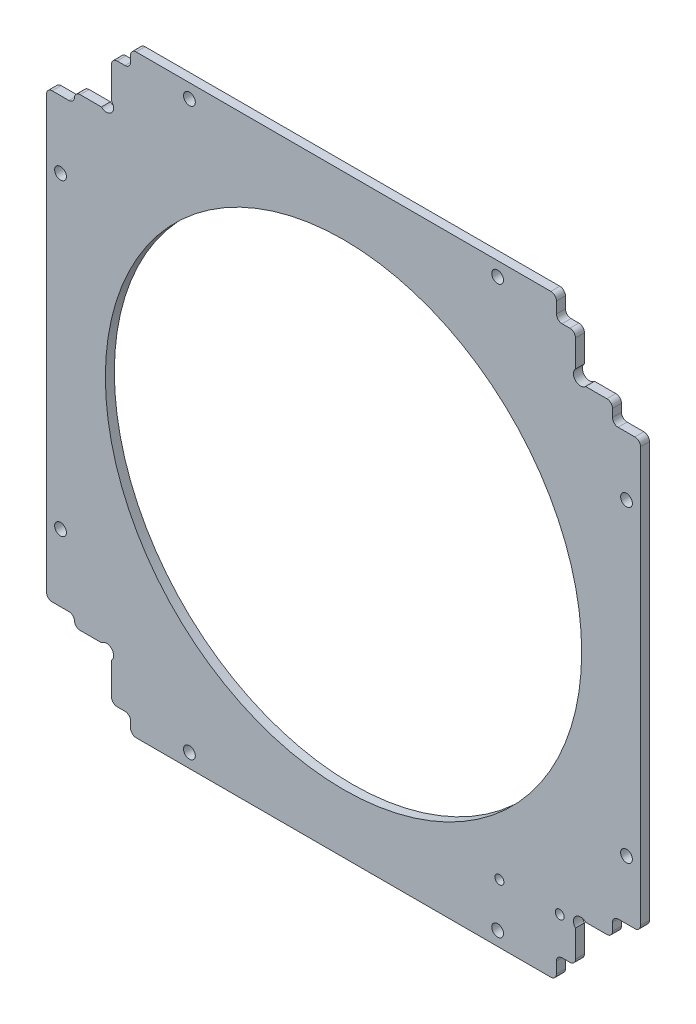
SolidWorks part; units mm, degrees
material "FR4_stuffedProtoboard"
ref_plane "Front Plane" through (0, 0, 0) normal (0, 0, 1) x (1, 0, 0)
ref_plane "Top Plane" through (0, 0, 0) normal (0, 1, 0) x (1, 0, 0)
ref_plane "Right Plane" through (0, 0, 0) normal (1, 0, 0) x (0, 0, -1)
sketch "Sketch1" plane through (0, 0, 0) normal (0, 0, 1) x (1, 0, 0)
  line L0 (53, 53) -> (-53, -53) construction
  line L1 (53, 53) -> (-53, 53)
  line L2 (53, 53) -> (53, -53)
  line L3 (53, -53) -> (-53, -53)
  line L4 (-53, 53) -> (-53, -53)
  point P4 (0, 0)
  dimension "D1" = 106
  dimension "D2" = 106
extrude "mainOutline" add sketch "Sketch1" along normal blind 1.6
sketch "axisLabels" plane through (0, 0, 0) normal (0, 0, -1) x (-1, 0, 0)
  text T0 "+Y"
  text T1 "+X"
sketch "Sketch4" plane through (0, 0, 0) normal (0, 0, -1) x (-1, 0, 0)
  line L1 (-41.4, -41.4) -> (-48, -41.4)
  line L3 (-41.4, -49) -> (-41.4, -41.4)
  line L5 (-60.1065, -39) -> (-49.9975, -39)
  line L7 (-39, -61.4521) -> (-39, -49.9)
  line L9 (39, -56.2753) -> (39, -49.9)
  line L10 (-53, 53) -> (53, 53) construction
  line L11 (41.4, -49.9) -> (41.4, -41.4)
  line L12 (-53, -53) -> (-53, 53) construction
  line L13 (41.4, -41.4) -> (48, -41.4)
  line L15 (48, -40.5) -> (55.5177, -40.5)
  line L17 (55.3838, 40.5) -> (48, 40.5)
  line L19 (39, 57.6877) -> (39, 49.9)
  line L21 (-39, 59.8804) -> (-39, 49.9)
  line L23 (-56.8428, 39) -> (-49.9975, 39)
  line L25 (-41.4, 41.4) -> (-41.4, 49)
  line L27 (-48, 41.4) -> (-41.4, 41.4)
  line L29 (41.4, 49.9) -> (41.4, 41.4)
  line L31 (48, 41.4) -> (41.4, 41.4)
  line L32 (-48, 41.4) -> (-48, 39)
  line L33 (-48, 39) -> (-49.9975, 39)
  line L34 (-41.4, 49) -> (-39, 49)
  line L35 (-39, 49) -> (-39, 49.9)
  line L36 (48, 40.5) -> (48, 41.4)
  line L37 (39, 49.9) -> (41.4, 49.9)
  line L38 (48, -40.5) -> (48, -41.4)
  line L39 (39, -49.9) -> (41.4, -49.9)
  line L40 (-41.4, -49) -> (-39, -49)
  line L41 (-39, -49) -> (-39, -49.9)
  line L42 (-49.9975, -39) -> (-48, -39)
  line L43 (-48, -39) -> (-48, -41.4)
  line L44 (-39, 59.8804) -> (-56.8428, 59.8804)
  line L45 (-56.8428, 59.8804) -> (-56.8428, 39)
  line L46 (53, 53) -> (53, -53) construction
  line L47 (-60.1065, -39) -> (-60.1065, -61.4521)
  line L48 (-60.1065, -61.4521) -> (-39, -61.4521)
  line L49 (39, -56.2753) -> (55.5177, -56.2753)
  line L50 (55.5177, -56.2753) -> (55.5177, -40.5)
  line L51 (55.3838, 40.5) -> (55.3838, 57.6877)
  line L52 (55.3838, 57.6877) -> (39, 57.6877)
  line L53 (53, -53) -> (-53, -53) construction
  dimension "D1" = 14
  dimension "D2" = 11.6
  dimension "D3" = 5
  dimension "D4" = 12.5
  dimension "D5" = 11.6
  dimension "D6" = 3.1
  dimension "D7" = 12.5
  dimension "D8" = 14
  dimension "D9" = 3.1
  dimension "D10" = 5
  dimension "D11" = 11.6
  dimension "D12" = 11.6
  dimension "D13" = 14
  dimension "D14" = 14
  dimension "D15" = 11.6
  dimension "D16" = 11.6
  dimension "D17" = 5
  dimension "D18" = 4
  dimension "D19" = 14
  dimension "D20" = 14
  dimension "D21" = 11.6
  dimension "D22" = 11.6
  dimension "D23" = 4
  dimension "D24" = 5
extrude "railCutouts" cut sketch "Sketch4" against normal through all
sketch "Sketch5" plane through (0, 0, 0) normal (0, 0, -1) x (-1, 0, 0)
  line L0 (-48.898, -39.898) -> (-52.4015, -43.4015) construction
  line L1 (-48, -40.7961) -> (-51.5035, -44.2995) construction
  line L2 (-49.7961, -39) -> (-53.2995, -42.5035) construction
  line L3 (-48, -41.4) -> (-48, -39) construction
  line L4 (-48, 39) -> (-48, 41.4) construction
  line L5 (-42.298, -42.298) -> (-45.4445, -45.4445) construction
  line L6 (-41.4, -43.1961) -> (-44.5465, -46.3425)
  line L7 (-43.1961, -41.4) -> (-46.3425, -44.5465)
  line L8 (-39.898, -49.898) -> (-42.6199, -52.6199) construction
  line L9 (-39, -50.7961) -> (-41.7219, -53.5179) construction
  line L10 (-40.7961, -49) -> (-43.5179, -51.7219) construction
  line L11 (39.898, -50.798) -> (41.4231, -52.3231) construction
  line L12 (40.7961, -49.9) -> (42.3212, -51.4251) construction
  line L13 (39, -51.6961) -> (40.5251, -53.2212) construction
  line L14 (42.298, -42.298) -> (44.0402, -44.0402) construction
  line L15 (43.1961, -41.4) -> (44.9382, -43.1422)
  line L16 (41.4, -43.1961) -> (43.1422, -44.9382)
  line L17 (48.898, -41.398) -> (49.9793, -42.4793) construction
  line L18 (49.7961, -40.5) -> (50.8774, -41.5813) construction
  line L19 (48, -42.2961) -> (49.0813, -43.3774) construction
  line L20 (48.898, 41.398) -> (50.5001, 43.0001) construction
  line L21 (48, 42.2961) -> (49.602, 43.8981) construction
  line L22 (49.7961, 40.5) -> (51.3981, 42.102) construction
  line L23 (42.298, 42.298) -> (44.029, 44.029) construction
  line L24 (41.4, 43.1961) -> (43.131, 44.927)
  line L25 (43.1961, 41.4) -> (44.927, 43.131)
  line L26 (39.898, 50.798) -> (41.2638, 52.1638) construction
  line L27 (39, 51.6961) -> (40.3658, 53.0618) construction
  line L28 (40.7961, 49.9) -> (42.1618, 51.2658) construction
  line L29 (-48.898, 39.898) -> (-50.0606, 41.0606) construction
  line L30 (-49.7961, 39) -> (-50.9587, 40.1626) construction
  line L31 (-48, 40.7961) -> (-49.1626, 41.9587) construction
  line L32 (-42.298, 42.298) -> (-43.7968, 43.7968) construction
  line L33 (-43.1961, 41.4) -> (-44.6948, 42.8988)
  line L34 (-41.4, 43.1961) -> (-42.8988, 44.6948)
  line L35 (-39.898, 49.898) -> (-41.256, 51.256) construction
  line L36 (-40.7961, 49) -> (-42.154, 50.358) construction
  line L37 (-39, 50.7961) -> (-40.358, 52.154) construction
  line L38 (-41.4, 41.4) -> (-41.4, 49) construction
  line L39 (-39, 49) -> (-39, 53) construction
  line L40 (39, 53) -> (39, 49.9) construction
  line L41 (41.4, 49.9) -> (41.4, 41.4) construction
  line L42 (48, 41.4) -> (48, 40.5) construction
  line L43 (39, -49.9) -> (39, -53) construction
  line L44 (41.4, -41.4) -> (41.4, -49.9) construction
  line L45 (53, -40.5) -> (48, -40.5) construction
  line L46 (-39, -53) -> (-39, -49) construction
  line L47 (-41.4, -49) -> (-41.4, -41.4) construction
  arc A0 (-48, -40.7961) -> (-49.7961, -39) centre (-48.898, -39.898) ccw construction
  arc A1 (-53.2995, -42.5035) -> (-51.5035, -44.2995) centre (-52.4015, -43.4015) ccw construction
  arc A2 (-41.4, -43.1961) -> (-43.1961, -41.4) centre (-42.298, -42.298) ccw
  arc A3 (-46.3425, -44.5465) -> (-44.5465, -46.3425) centre (-45.4445, -45.4445) ccw
  arc A4 (-39, -50.7961) -> (-40.7961, -49) centre (-39.898, -49.898) ccw construction
  arc A5 (-43.5179, -51.7219) -> (-41.7219, -53.5179) centre (-42.6199, -52.6199) ccw construction
  arc A6 (40.7961, -49.9) -> (39, -51.6961) centre (39.898, -50.798) ccw construction
  arc A7 (40.5251, -53.2212) -> (42.3212, -51.4251) centre (41.4231, -52.3231) ccw construction
  arc A8 (43.1961, -41.4) -> (41.4, -43.1961) centre (42.298, -42.298) ccw
  arc A9 (43.1422, -44.9382) -> (44.9382, -43.1422) centre (44.0402, -44.0402) ccw
  arc A10 (49.7961, -40.5) -> (48, -42.2961) centre (48.898, -41.398) ccw construction
  arc A11 (49.0813, -43.3774) -> (50.8774, -41.5813) centre (49.9793, -42.4793) ccw construction
  arc A12 (48, 42.2961) -> (49.7961, 40.5) centre (48.898, 41.398) ccw construction
  arc A13 (51.3981, 42.102) -> (49.602, 43.8981) centre (50.5001, 43.0001) ccw construction
  arc A14 (41.4, 43.1961) -> (43.1961, 41.4) centre (42.298, 42.298) ccw
  arc A15 (44.927, 43.131) -> (43.131, 44.927) centre (44.029, 44.029) ccw
  arc A16 (39, 51.6961) -> (40.7961, 49.9) centre (39.898, 50.798) ccw construction
  arc A17 (42.1618, 51.2658) -> (40.3658, 53.0618) centre (41.2638, 52.1638) ccw construction
  arc A18 (-49.7961, 39) -> (-48, 40.7961) centre (-48.898, 39.898) ccw construction
  arc A19 (-49.1626, 41.9587) -> (-50.9587, 40.1626) centre (-50.0606, 41.0606) ccw construction
  arc A20 (-43.1961, 41.4) -> (-41.4, 43.1961) centre (-42.298, 42.298) ccw
  arc A21 (-42.8988, 44.6948) -> (-44.6948, 42.8988) centre (-43.7968, 43.7968) ccw
  arc A22 (-40.7961, 49) -> (-39, 50.7961) centre (-39.898, 49.898) ccw construction
  arc A23 (-40.358, 52.154) -> (-42.154, 50.358) centre (-41.256, 51.256) ccw construction
  point P2 (-50.6498, -41.6498)
  point P9 (-43.8713, -43.8713)
  point P17 (-41.259, -51.259)
  point P24 (40.6606, -51.5606)
  point P31 (43.1691, -43.1691)
  point P38 (49.4387, -41.9387)
  point P45 (49.699, 42.199)
  point P52 (43.1635, 43.1635)
  point P59 (40.5809, 51.4809)
  point P66 (-49.4793, 40.4793)
  point P73 (-43.0474, 43.0474)
  point P80 (-40.577, 50.577)
  dimension "D14" = 1.27
  dimension "D1" = 45
  dimension "D3" = 45
  dimension "D4" = 45
  dimension "D5" = 45
  dimension "D6" = 45
  dimension "D7" = 45
  dimension "D8" = 45
  dimension "D9" = 45
  dimension "D10" = 45
  dimension "D11" = 45
  dimension "D12" = 45
  dimension "D13" = 45
extrude "dogbones" cut sketch "Sketch5" against normal through all
sketch "Sketch6" plane through (0, 0, 0) normal (0, 0, -1) x (-1, 0, 0)
  line L0 (-39, 50) -> (-39, 53) construction
  line L1 (-39, 49) -> (-39, 53) construction
  line L2 (-39, 53) -> (39, 53) construction
  line L3 (-40, 50) -> (-40, 53)
  line L4 (-38, 50) -> (-38, 53)
  line L5 (-49, 39) -> (-53, 39) construction
  line L6 (-53, 39) -> (-48, 39) construction
  line L7 (-49, 38) -> (-53, 38)
  line L8 (-49, 40) -> (-53, 40)
  line L9 (-49, -39) -> (-55.2142, -39) construction
  line L10 (-48, -39) -> (-53, -39) construction
  line L11 (-49, -40) -> (-55.2142, -40)
  line L12 (-49, -38) -> (-55.2142, -38)
  line L13 (-39, -50) -> (-39, -53.9161) construction
  line L14 (-39, -53) -> (-39, -49) construction
  line L15 (-38, -50) -> (-38, -53.9161)
  line L16 (-40, -50) -> (-40, -53.9161)
  line L17 (39, -50.9) -> (39, -54.538) construction
  line L18 (39, -49.9) -> (39, -53) construction
  line L19 (40, -50.9) -> (40, -54.538)
  line L20 (38, -50.9) -> (38, -54.538)
  line L21 (49, -40.5) -> (54.2026, -40.5) construction
  line L22 (53, -40.5) -> (48, -40.5) construction
  line L23 (49, -39.5) -> (54.2026, -39.5)
  line L24 (49, -41.5) -> (54.2026, -41.5)
  line L25 (49, 40.5) -> (54.5566, 40.5) construction
  line L26 (48, 40.5) -> (53, 40.5) construction
  line L27 (49, 41.5) -> (54.5566, 41.5)
  line L28 (49, 39.5) -> (54.5566, 39.5)
  line L29 (39, 50.9) -> (39, 55.8281) construction
  line L30 (39, 53) -> (39, 49.9) construction
  line L31 (38, 50.9) -> (38, 55.8281)
  line L32 (40, 50.9) -> (40, 55.8281)
  line L33 (-48, -41.4) -> (-48, -39) construction
  line L34 (-39, -49) -> (-41.4, -49) construction
  line L35 (41.4, -49.9) -> (39, -49.9) construction
  line L36 (48, -40.5) -> (48, -41.4) construction
  line L37 (48, 41.4) -> (48, 40.5) construction
  line L38 (39, 49.9) -> (41.4, 49.9) construction
  arc A0 (-40, 50) -> (-38, 50) centre (-39, 50) ccw
  arc A1 (-38, 53) -> (-40, 53) centre (-39, 53) ccw
  arc A2 (-49, 38) -> (-49, 40) centre (-49, 39) ccw
  arc A3 (-53, 40) -> (-53, 38) centre (-53, 39) ccw
  arc A4 (-49, -40) -> (-49, -38) centre (-49, -39) ccw
  arc A5 (-55.2142, -38) -> (-55.2142, -40) centre (-55.2142, -39) ccw
  arc A6 (-38, -50) -> (-40, -50) centre (-39, -50) ccw
  arc A7 (-40, -53.9161) -> (-38, -53.9161) centre (-39, -53.9161) ccw
  arc A8 (40, -50.9) -> (38, -50.9) centre (39, -50.9) ccw
  arc A9 (38, -54.538) -> (40, -54.538) centre (39, -54.538) ccw
  arc A10 (49, -39.5) -> (49, -41.5) centre (49, -40.5) ccw
  arc A11 (54.2026, -41.5) -> (54.2026, -39.5) centre (54.2026, -40.5) ccw
  arc A12 (49, 41.5) -> (49, 39.5) centre (49, 40.5) ccw
  arc A13 (54.5566, 39.5) -> (54.5566, 41.5) centre (54.5566, 40.5) ccw
  arc A14 (38, 50.9) -> (40, 50.9) centre (39, 50.9) ccw
  arc A15 (40, 55.8281) -> (38, 55.8281) centre (39, 55.8281) ccw
  point P6 (-39, 51.5)
  point P11 (-51, 39)
  point P21 (-52.1071, -39)
  point P30 (-39, -51.958)
  point P39 (39, -52.719)
  point P48 (51.6013, -40.5)
  point P57 (51.7783, 40.5)
  point P66 (39, 53.364)
  point P75 (-39, 49)
  dimension "D1" = 1
extrude "solarFillets" cut sketch "Sketch6" against normal through all
fillet "handlingFillets" radius 1 16 edges at (-41.4, -49.9, 0.8) (-38, -53, 0.8) (-53, -39.5, 0.8) (-48, -41.4, 0.8) (-48, 41.4, 0.8) (-53, 39.5, 0.8) (-41.4, 49.9, 0.8) (-38, 53, 0.8) (38, 53, 0.8) (41.4, 49, 0.8) (48, 41.4, 0.8) (53, 38, 0.8) (53, -38, 0.8) (48, -41.4, 0.8) (41.4, -49, 0.8) (38, -53, 0.8)
sketch "Sketch7" plane through (0, 0, 1.6) normal (0, 0, 1) x (1, 0, 0)
  line L0 (-37, -53) -> (37, -53) construction
  line L1 (-53, 38.5) -> (-53, -38.5) construction
  line L2 (37, 53) -> (-37, 53) construction
  line L3 (-31.37, 28.67) -> (-31.37, 31.21) construction
  line L4 (-31.37, 31.21) -> (-28.83, 31.21) construction
  line L5 (-28.83, 31.21) -> (-28.83, 28.67) construction
  line L6 (-28.83, 28.67) -> (-31.37, 28.67) construction
  line L7 (-31.37, 28.67) -> (-28.83, 31.21) construction
  circle A1 centre (-28.4723, -17.925) radius 0.8
  circle A3 centre (-28.4723, -33.775) radius 0.8
  circle A5 centre (-31.37, 28.67) radius 0.425
  circle A7 centre (-28.83, 28.67) radius 0.425
  circle A9 centre (-30.1, 29.94) radius 0.425
  circle A10 centre (-28.83, 31.21) radius 0.425
  circle A11 centre (-31.37, 31.21) radius 0.425
  circle A12 centre (-31.37, 21.27) radius 0.425
  circle A13 centre (-28.83, 21.27) radius 0.425
  circle A14 centre (-30.1, 22.54) radius 0.425
  circle A15 centre (-28.83, 23.81) radius 0.425
  circle A16 centre (-31.37, 23.81) radius 0.425
  circle A17 centre (-31.37, 13.87) radius 0.425
  circle A18 centre (-28.83, 13.87) radius 0.425
  circle A19 centre (-30.1, 15.14) radius 0.425
  circle A20 centre (-28.83, 16.41) radius 0.425
  circle A21 centre (-31.37, 16.41) radius 0.425
  point P13 (-30.1, 29.94)
  dimension "D8" = 1.6
  dimension "D9" = 3
  dimension "D6" = 0.85
  dimension "D1" = 19.225
  dimension "D2" = 24.5277
  dimension "D3" = 15.85
  dimension "D4" = 23.06
  dimension "D5" = 22.9
  dimension "D7" = 2.54
  dimension "D10" = 7.4
extrude "connectorHoles" [suppressed] cut sketch "Sketch7" against normal through all
hole_wizard "M2 Clearance Hole1" positions "Sketch8" profile "Sketch9" hole size "M2" standard "ANSI Metric" end condition through all
sketch "Sketch8" plane through (0, 0, 0) normal (0, 0, -1) x (-1, 0, 0)
  line L0 (53, 38.5) -> (53, -38.5) construction
  line L1 (37, -53) -> (-37, -53) construction
  line L2 (-53, -37) -> (-53, 37) construction
  line L3 (53, 0) -> (-53, 0) construction
  line L5 (0, -53) -> (0, -11.6379) construction
  point P0 (50.5, -27.5)
  point P1 (27.5, -50.5)
  point P5 (-50.5, -27.5)
  point P30 (-27.5, -50.5)
  point P31 (-27.5, 50.5)
  point P32 (-50.5, 27.5)
  point P33 (27.5, 50.5)
  point P34 (50.5, 27.5)
  dimension "D1" = 2.5
  dimension "D2" = 2.5
  dimension "D3" = 55
  dimension "D4" = 2.5
  dimension "D5" = 55
  dimension "D6" = 55
sketch "Sketch9" plane through (-50.5, -27.5, 0) normal (1, 0, 0) x (0, 1, 0)
  line L0 (0, 0) -> (0, 1.6)
  line L1 (0, 1.6) -> (1.05, 1.6)
  line L2 (1.05, 1.6) -> (1.05, 0)
  line L5 (1.05, 0) -> (0, 0)
  line L11 (0, -6.35) -> (0, 107.95) construction
  dimension "Thru Hole Dia." = 2.1
  dimension "Thru Hole Depth" = 1.6
sketch "Sketch10" plane through (0, 0, 0) normal (0, 0, -1) x (-1, 0, 0)
  circle A0 centre (0, 0) radius 42.5
  dimension "D1" = 85
extrude "Cut-Extrude1" cut sketch "Sketch10" against normal through all both and the other way through all
sketch "Sketch11" [suppressed] plane through (0, 0, 0) normal (0, 0, -1) x (-1, 0, 0)
  circle A0 centre (0, 0) radius 22.5
  dimension "D1" = 45
extrude "Cut-Extrude2" [suppressed] cut sketch "Sketch11" against normal through all both and the other way through all
sketch "Sketch12" plane through (0, 0, 1.6) normal (0, 0, 1) x (1, 0, 0)
  line L1 (-37, -53) -> (37, -53) construction
  line L2 (53, -37) -> (53, 37) construction
  circle A0 centre (27.815, -42.5) radius 0.8
  circle A1 centre (38.585, -42.5) radius 0.8
  dimension "D1" = 1.6
  dimension "D2" = 10.77
  dimension "D3" = 10.5
  dimension "D4" = 25.185
extrude "Cut-Extrude3" cut sketch "Sketch12" against normal through all both and the other way through all
